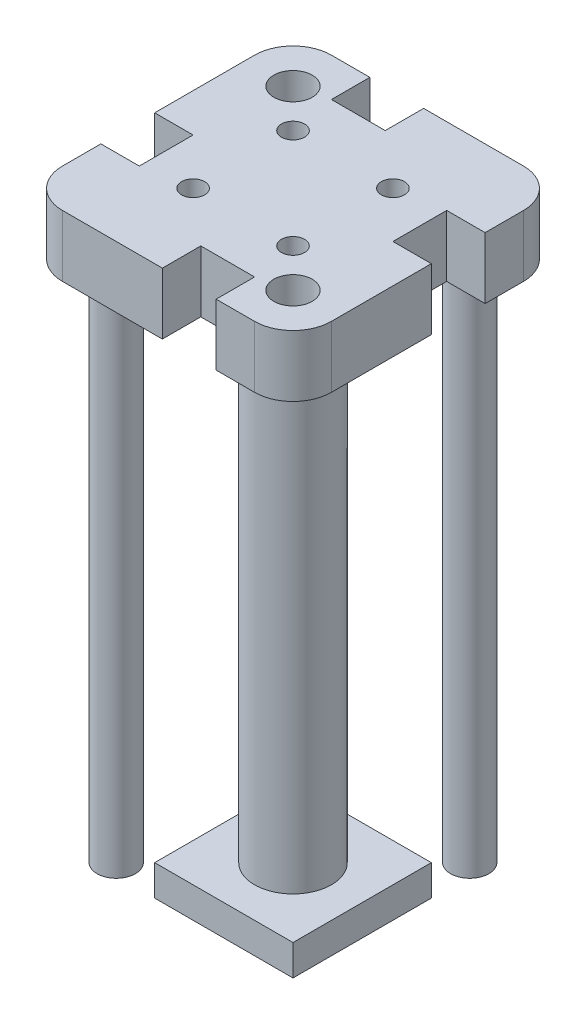
SolidWorks part; units mm, degrees
ref_plane "Front Plane" through (0, 0, 0) normal (0, 0, 1) x (1, 0, 0)
ref_plane "Top Plane" through (0, 0, 0) normal (0, 1, 0) x (1, 0, 0)
ref_plane "Right Plane" through (0, 0, 0) normal (1, 0, 0) x (0, 0, -1)
sketch "Sketch1" plane through (0, 0, 0) normal (0, 1, 0) x (1, 0, 0)
  line L1 (0, 0) -> (35, 0)
  line L2 (0, 0) -> (0, 35)
  line L3 (0, 35) -> (35, 35)
  line L4 (35, 0) -> (35, 35)
  dimension "D1" = 35
  dimension "D2" = 35
extrude "Boss-Extrude1" add sketch "Sketch1" along normal blind 8
sketch "Sketch2" plane through (0, 0, 0) normal (0, -1, 0) x (1, 0, 0)
  line L0 (0, 0) -> (35, 0) construction
  line L1 (18, 0) -> (25, 0)
  line L2 (18, 0) -> (18, -5)
  line L3 (18, -5) -> (25, -5)
  line L4 (25, 0) -> (25, -5)
  line L5 (35, -35) -> (0, -35) construction
  line L6 (10, -35) -> (17, -35)
  line L7 (10, -35) -> (10, -30)
  line L8 (10, -30) -> (17, -30)
  line L9 (17, -35) -> (17, -30)
  line L10 (0, -35) -> (0, 0) construction
  line L11 (0, -10) -> (5, -10)
  line L12 (0, -10) -> (0, -17)
  line L13 (0, -17) -> (5, -17)
  line L14 (5, -10) -> (5, -17)
  line L15 (35, 0) -> (35, -35) construction
  line L16 (35, -18) -> (30, -18)
  line L17 (35, -18) -> (35, -25)
  line L18 (35, -25) -> (30, -25)
  line L19 (30, -18) -> (30, -25)
  circle A0 centre (6, -6) radius 2.5
  circle A1 centre (29, -6) radius 4
  circle A2 centre (6, -29) radius 4
  circle A3 centre (29, -29) radius 2.5
  circle A4 centre (17.5, -17.5) radius 5
  circle A5 centre (11, -11) radius 1.5
  circle A6 centre (24, -11) radius 1.5
  circle A7 centre (24, -24) radius 1.5
  circle A8 centre (11, -24) radius 1.5
  point P45 (17.5, 0)
  point P46 (35, -17.5)
  line M26 (0, 0) -> (0, -35)
  line M27 (0, -35) -> (35, -35)
  line M28 (35, -35) -> (35, 0)
  line M29 (35, 0) -> (0, 0)
  dimension "D7" = 5
  dimension "D8" = 5
  dimension "D9" = 8
  dimension "D10" = 8
  dimension "D11" = 10
  dimension "D12" = 3
  dimension "D13" = 3
  dimension "D14" = 3
  dimension "D15" = 3
  dimension "D1" = 5
  dimension "D2" = 7
  dimension "D3" = 10
  dimension "D4" = 10
  dimension "D5" = 10
  dimension "D6" = 10
  dimension "D16" = 6
  dimension "D17" = 6
  dimension "D18" = 6
  dimension "D19" = 6
  dimension "D20" = 6
  dimension "D21" = 6
  dimension "D22" = 6
  dimension "D23" = 11
  dimension "D24" = 6
  dimension "D25" = 11
extrude "Cut-Extrude1" cut sketch "Sketch2" against normal through all contours L16 L19 L18 M28 | L9 L8 L7 M27 | L14 L11 L13 M26 | L4 L2 L3 M29 | A5 | A6 | A8 | A7 region at (21.5, 0, -2.5) region at (2.5, 0, -13.5) region at (32.5, 0, -21.5) region at (13.5, 0, -32.5) region at (11, 0, -11) region at (24, 0, -11) region at (24, 0, -24) region at (11, 0, -24)
extrude "Cut-Extrude2" cut sketch "Sketch2<5>" against normal blind 4 contours A2 | A1 | A5 region at (6, 0, -29)
sketch "Sketch2<5>" plane through (0, 0, 0) normal (0, -1, 0) x (1, 0, 0) same geometry as "Sketch2"
extrude "Boss-Extrude2" add sketch "Sketch2<7>" along normal blind 68 contours A4 | A3 | A0 region at (29, 0, -29) region at (17.5, 0, -17.5)
sketch "Sketch2<7>" plane through (0, 0, 0) normal (0, -1, 0) x (1, 0, 0) same geometry as "Sketch2"
sketch "Sketch3" plane through (0, -68, 0) normal (0, -1, 0) x (-1, 0, 0)
  line L0 (0, 10) -> (0, 0) construction
  line L1 (-8.5, 8.5) -> (-26.5, 8.5)
  line L2 (-8.5, 8.5) -> (-8.5, 26.5)
  line L3 (-8.5, 26.5) -> (-26.5, 26.5)
  line L4 (-26.5, 8.5) -> (-26.5, 26.5)
  line L5 (-25, 0) -> (-35, 0) construction
  line L6 (-35, 0) -> (-35, 18) construction
  line L7 (-35, 35) -> (-17, 35) construction
  dimension "D1" = 8.5
  dimension "D2" = 8.5
  dimension "D3" = 8.5
  dimension "D4" = 8.5
extrude "Boss-Extrude3" add sketch "Sketch3" along normal blind 4
fillet "Fillet1" radius 5 4 edges at (35, 4, -35) (0, 4, -35) (0, 4, 0) (35, 4, 0)
sketch "Sketch4" plane through (0, 4, 0) normal (0, -1, 0) x (-1, 0, 0)
  circle A0 centre (-29, 6) radius 2.5
  circle A1 centre (-6, 29) radius 2.5
  dimension "D1" = 5
extrude "Cut-Extrude3" cut sketch "Sketch4" against normal blind 10
